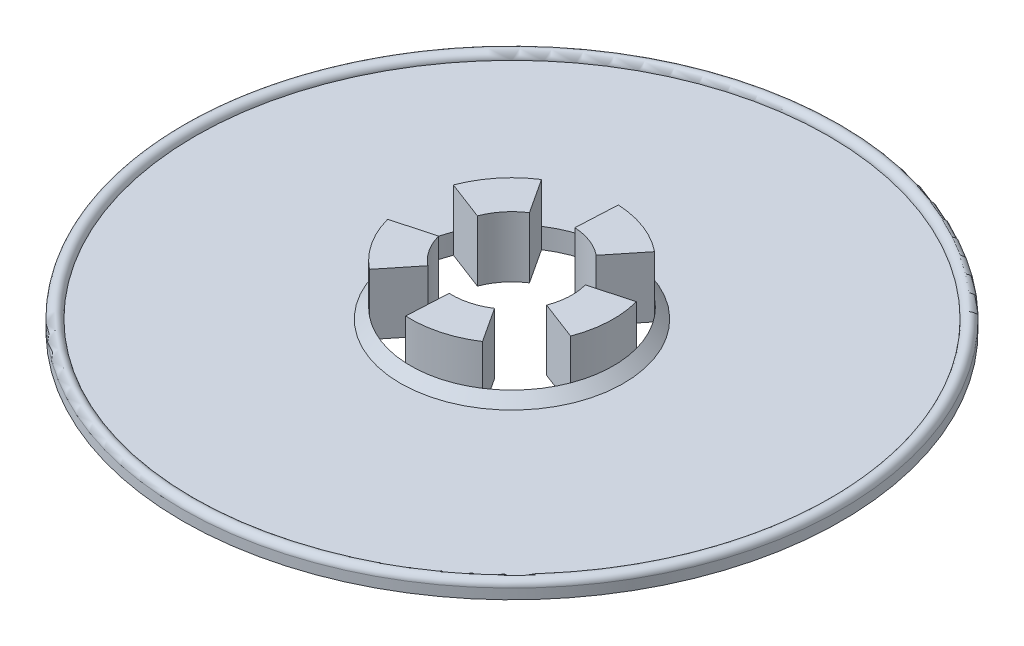
SolidWorks part; units mm, degrees
ref_plane "Front Plane" through (0, 0, 0) normal (0, 0, 1) x (1, 0, 0)
ref_plane "Top Plane" through (0, 0, 0) normal (0, 1, 0) x (1, 0, 0)
ref_plane "Right Plane" through (0, 0, 0) normal (1, 0, 0) x (0, 0, -1)
sketch "Sketch1" plane through (0, 0, 0) normal (0, 1, 0) x (1, 0, 0)
  circle A0 centre (0, 0) radius 41.275
  dimension "D1" = 82.55
extrude "Boss-Extrude1" add sketch "Sketch1" along normal blind 1.27
sketch "Sketch6" plane through (0, 1.27, 0) normal (0, 1, 0) x (1, 0, 0)
  circle A0 centre (0, 0) radius 12.7
  dimension "D1" = 25.4
extrude "Boss-Extrude3" add sketch "Sketch6" along normal blind 6.35
chamfer "Chamfer2" distance 1.27 angle 45 1 edges at (0, 1.27, 12.7)
sketch "Sketch4" plane through (0, 0, 0) normal (0, -1, 0) x (1, 0, 0)
  line L0 (6.9396, 10.6363) -> (4.0982, 6.2813)
  line L1 (11.8662, 4.526) -> (7.0076, 2.6728)
  line L2 (12.2602, -3.3132) -> (7.2403, -1.9566)
  line L3 (7.9713, -9.8868) -> (4.7075, -5.8387)
  line L4 (0.6376, -12.684) -> (0.3765, -7.4905)
  line L5 (-6.9396, -10.6363) -> (-4.0982, -6.2813)
  line L6 (-11.8662, -4.526) -> (-7.0076, -2.6728)
  line L7 (-12.2602, 3.3132) -> (-7.2403, 1.9566)
  line L10 (-7.9713, 9.8868) -> (-4.7075, 5.8387)
  line L11 (-0.6376, 12.684) -> (-0.3765, 7.4905)
  circle A0 centre (0, 0) radius 12.7 construction
  arc A1 (7.0076, 2.6728) -> (4.0982, 6.2813) centre (0, 0) ccw
  arc A2 (11.8662, 4.526) -> (6.9396, 10.6363) centre (0, 0) ccw
  arc A3 (4.7075, -5.8387) -> (7.2403, -1.9566) centre (0, 0) ccw
  arc A4 (7.9713, -9.8868) -> (12.2602, -3.3132) centre (0, 0) ccw
  arc A5 (-4.0982, -6.2813) -> (0.3765, -7.4905) centre (0, 0) ccw
  arc A6 (-6.9396, -10.6363) -> (0.6376, -12.684) centre (0, 0) ccw
  arc A7 (-7.2403, 1.9566) -> (-7.0076, -2.6728) centre (0, 0) ccw
  arc A8 (-12.2602, 3.3132) -> (-11.8662, -4.526) centre (0, 0) ccw
  arc A10 (-0.6376, 12.684) -> (-7.9713, 9.8868) centre (0, 0) ccw
  arc A13 (7.0076, 2.6728) -> (4.0982, 6.2813) centre (0, 0) ccw
  arc A14 (4.7075, -5.8387) -> (7.2403, -1.9566) centre (0, 0) ccw
  arc A16 (-4.0982, -6.2813) -> (0.3765, -7.4905) centre (0, 0) ccw
  arc A17 (-7.2403, 1.9566) -> (-7.0076, -2.6728) centre (0, 0) ccw
  circle A20 centre (0, 0) radius 7.5
  circle A21 centre (0, 0) radius 41.275 construction
  point P40 (0, 0)
  dimension "D1" = 36
  dimension "D2" = 7.5
  dimension "D3" = 12.7
extrude "Cut-Extrude2" cut sketch "Sketch4" against normal through all contours L11 A10 L10 | L1 A2 L0 A1 | L3 A4 L2 A3 | L5 A6 L4 A5 | L7 A8 L6 A7 | A5 A20 A3 A1 A7 region at (7.9049, 0, 6.3733) region at (0, 0, 0) region at (-3.6187, 0, 9.4874) region at (8.5042, 0, -5.5485) region at (-10.1413, 0, -0.5098) region at (-2.649, 0, -9.8025)
sketch "Sketch7" plane through (0, 0, 0) normal (0, 0, 1) x (1, 0, 0)
  line L0 (41.275, 1.27) -> (-41.275, 1.27) construction
  line L1 (-41.275, 1.27) -> (-39.685, 1.27)
  arc A0 (-39.685, 1.27) -> (-41.275, 1.27) centre (-40.48, 1.27) ccw
  dimension "D1" = 1.59
ref_axis "Axis1" through (0, 8.001, 0) along (0, -1, 0)
revolve "Revolve1" add sketch "Sketch7" angle 360 about axis through (0, 8.001, 0) along (0, -1, 0)
